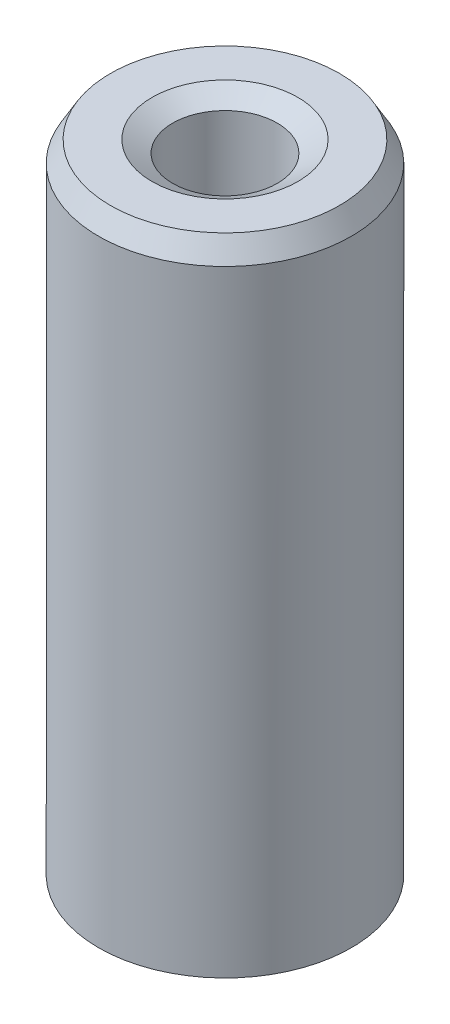
SolidWorks part; units mm, degrees
ref_plane "Front Plane" through (0, 0, 0) normal (0, 0, 1) x (1, 0, 0)
ref_plane "Top Plane" through (0, 0, 0) normal (0, 1, 0) x (1, 0, 0)
ref_plane "Right Plane" through (0, 0, 0) normal (1, 0, 0) x (0, 0, -1)
sketch "Sketch1" plane through (0, 0, 0) normal (0, 1, 0) x (1, 0, 0)
  circle A0 centre (0, 0) radius 20
  dimension "SLEEVE_OD" = 40
extrude "Boss-Extrude1" add sketch "Sketch1" along normal blind 102.6321
sketch "Sketch2" plane through (0, 0, 0) normal (0, 1, 0) x (1, 0, 0)
  circle A0 centre (0, 0) radius 8.2727
  dimension "BORE_D" = 16.5454
extrude "Cut-Extrude1" cut sketch "Sketch2" along normal through all
chamfer "Chamfer1" distance 3.2669 angle 30 4 edges at (0, 102.6321, 8.2727) (0, 0, 8.2727) (0, 0, 20) (0, 102.6321, 20) first distance on face at (0, 102.6321, 8.2727) first distance on face at (0, 0, 8.2727) first distance on face at (0, 102.6321, 20)
